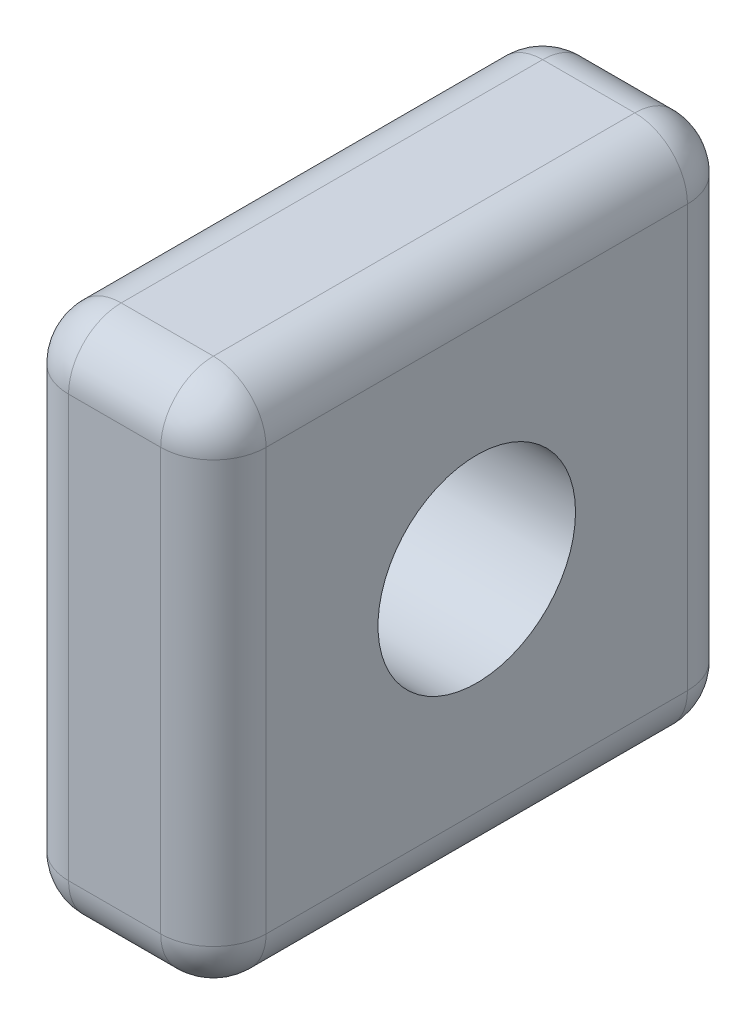
SolidWorks part; units mm, degrees
ref_plane "Front Plane" through (0, 0, 0) normal (0, 0, 1) x (1, 0, 0)
ref_plane "Top Plane" through (0, 0, 0) normal (0, 1, 0) x (1, 0, 0)
ref_plane "Right Plane" through (0, 0, 0) normal (1, 0, 0) x (0, 0, -1)
sketch "Sketch2" plane through (0, 0, 0) normal (1, 0, 0) x (0, 0, -1)
  line L1 (0, 0) -> (12.7, 0)
  line L2 (0, 0) -> (0, 12.7)
  line L3 (0, 12.7) -> (12.7, 12.7)
  line L4 (12.7, 0) -> (12.7, 12.7)
extrude "Boss-Extrude4" add sketch "Sketch2" along normal blind 4.7625
sketch "Sketch3" plane through (4.7625, 0, 0) normal (1, 0, 0) x (0, 0, -1)
  circle A0 centre (6.35, 6.35) radius 2.3813
extrude "Cut-Extrude1" cut sketch "Sketch3" against normal through all contours A0
fillet "Fillet1" radius 1.27 4 edges at (4.7625, 6.35, -12.7) (4.7625, 0, -6.35) (4.7625, 6.35, 0) (4.7625, 12.7, -6.35)
fillet "Fillet2" radius 1.27 13 edges at (4.3905, 0.372, -0.372) (4.3905, 12.328, -0.372) (4.3905, 0.372, -12.328) (4.3905, 12.328, -12.328) (0, 6.35, -8.7313) (0, 6.35, 0) (0, 0, -6.35) (1.7463, 0, 0) (0, 12.7, -6.35) (1.7463, 12.7, 0) (0, 6.35, -12.7) (1.7463, 0, -12.7) (1.7463, 12.7, -12.7)
